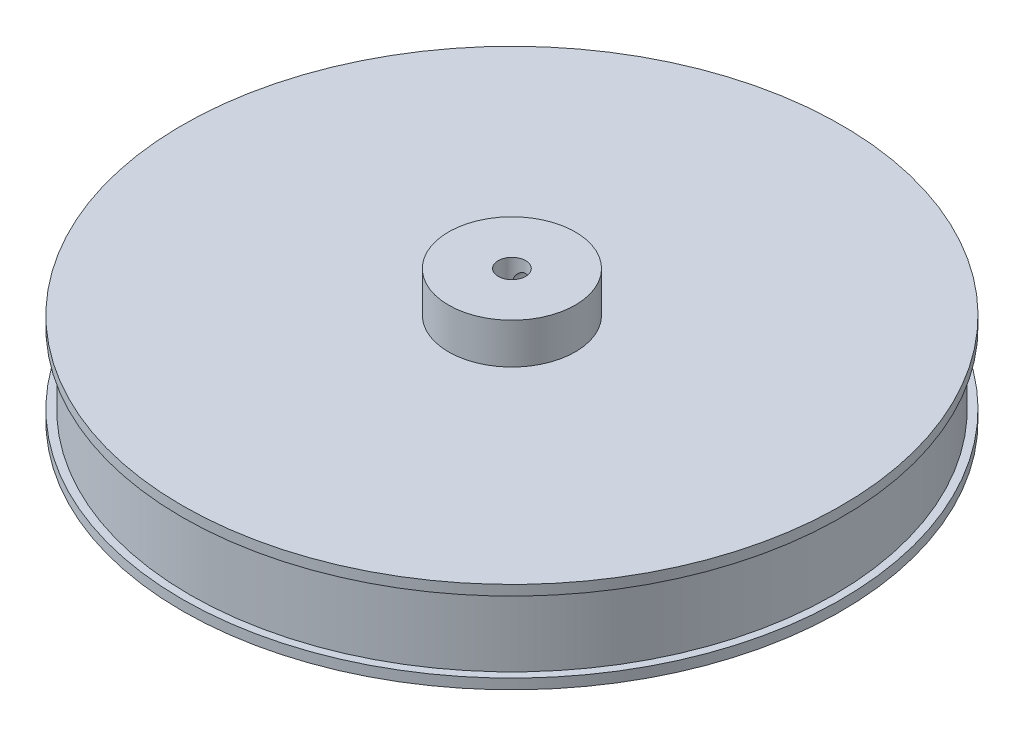
SolidWorks part; units mm, degrees
ref_plane "Front Plane" through (0, 0, 0) normal (0, 0, 1) x (1, 0, 0)
ref_plane "Top Plane" through (0, 0, 0) normal (0, 1, 0) x (1, 0, 0)
ref_plane "Right Plane" through (0, 0, 0) normal (1, 0, 0) x (0, 0, -1)
sketch "Sketch1" plane through (0, 0, 0) normal (0, 1, 0) x (1, 0, 0)
  circle A0 centre (0, 0) radius 32.5
  circle A1 centre (0, 0) radius 6.25
  circle A2 centre (0, 0) radius 1.35
  dimension "D1" = 2.7
  dimension "D2" = 65
  dimension "D3" = 12.5
extrude "Boss-Extrude1" add sketch "Sketch1" along normal blind 9 contours A2 | A0 region at (0, 0, 0)
extrude "Boss-Extrude2" add sketch "Sketch1<3>" along normal blind 4 from surface contours A1 A2 region at (-6.0732, 0, 0) starting at face at (0, 9, 32.5)
sketch "Sketch1<3>" plane through (0, 0, 0) normal (0, 1, 0) x (1, 0, 0) same geometry as "Sketch1"
sketch "Sketch2" plane through (0, 0, 0) normal (0, 0, 1) x (1, 0, 0)
  line L0 (32.5, 0) -> (32.5, 9) construction
  line L1 (32.5, 8) -> (31.75, 8)
  line L2 (32.5, 8) -> (32.5, 1)
  line L3 (32.5, 1) -> (31.75, 1)
  line L4 (31.75, 8) -> (31.75, 1)
  line L5 (32.5, 9) -> (-32.5, 9) construction
  line L6 (-32.5, 0) -> (32.5, 0) construction
  dimension "D1" = 1
  dimension "D2" = 1
  dimension "D3" = 0.75
revolve "Cut-Revolve1" cut sketch "Sketch2" angle 360 about axis through (0, 9, 0) along (0, -1, 0)
sketch "Sketch3" plane through (0, 0, 0) normal (0, 0, 1) x (1, 0, 0)
  line L0 (0, 13) -> (0, 0) construction
  line L1 (6.25, 13) -> (-6.25, 13) construction
  circle A0 centre (0, 11) radius 0.9
  dimension "D1" = 1.8
  dimension "D2" = 2
extrude "Cut-Extrude1" cut sketch "Sketch3" against normal blind 10
